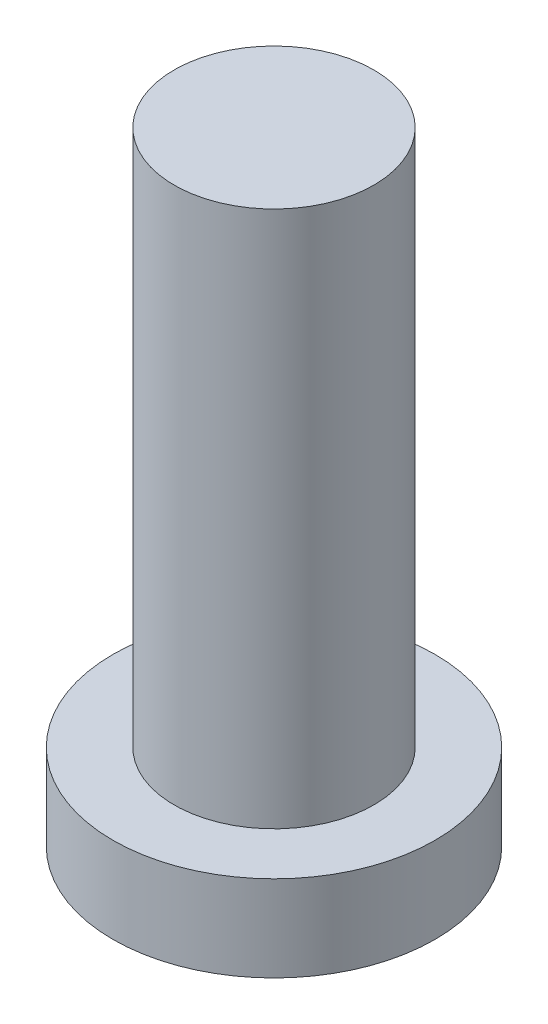
SolidWorks part; units mm, degrees
ref_plane "Front Plane" through (0, 0, 0) normal (0, 0, 1) x (1, 0, 0)
ref_plane "Top Plane" through (0, 0, 0) normal (0, 1, 0) x (1, 0, 0)
ref_plane "Right Plane" through (0, 0, 0) normal (1, 0, 0) x (0, 0, -1)
sketch "Sketch1" plane through (0, 0, 0) normal (0, 1, 0) x (1, 0, 0)
  circle A0 centre (0, 0) radius 7.5
  dimension "D1" = 15
extrude "Boss-Extrude3" add sketch "Sketch1" along normal blind 4
sketch "Sketch4" plane through (0, 4, 0) normal (0, 1, 0) x (1, 0, 0)
  circle A0 centre (0, 0) radius 4.65
  dimension "D1" = 9.3
extrude "Boss-Extrude4" add sketch "Sketch4" along normal blind 21
sketch "Sketch7" plane through (0, 25, 0) normal (0, 1, 0) x (1, 0, 0)
  circle A0 centre (0, 0) radius 4.65
extrude "Boss-Extrude5" add sketch "Sketch7" along normal blind 4
